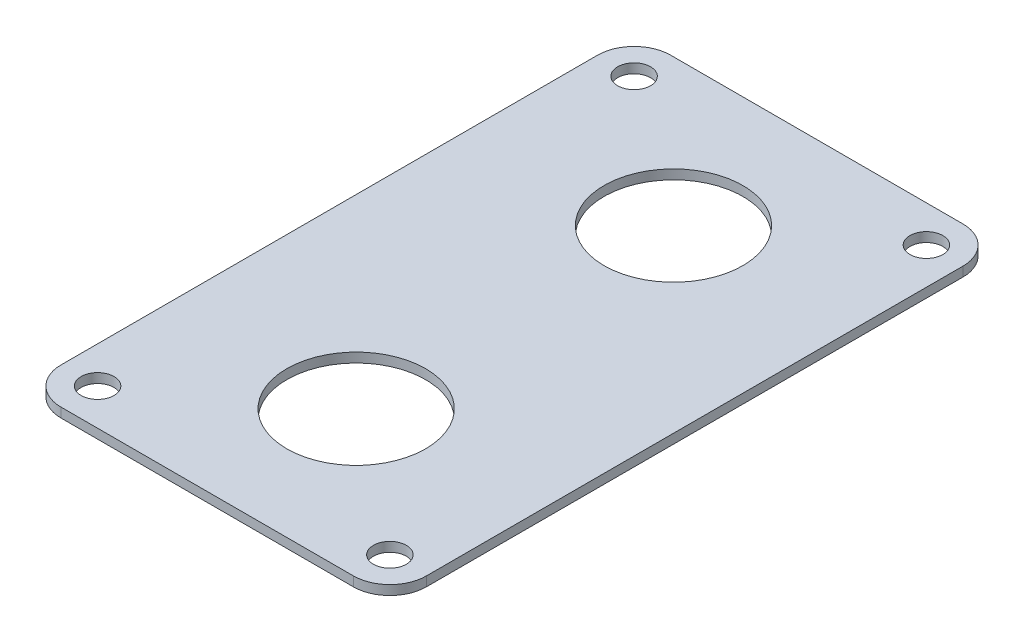
SolidWorks part; units mm, degrees
note: The reader was unsure of these and kept them because the rebuilt part matched: thickness of "Base-Flange1", "Sheet-Metal1", "Sheet-Metal2", "Sheet-Metal3".
material "AISI 1015 Steel, Cold Drawn (SS)"
ref_plane "Front Plane" through (0, 0, 0) normal (0, 0, 1) x (1, 0, 0)
ref_plane "Top Plane" through (0, 0, 0) normal (0, 1, 0) x (1, 0, 0)
ref_plane "Right Plane" through (0, 0, 0) normal (1, 0, 0) x (0, 0, -1)
sketch "Sketch1" plane through (0, 0, 0) normal (0, 1, 0) x (1, 0, 0)
  line L0 (9.6129, 37) -> (-10.3871, 37) construction
  line L1 (-25.3871, 42) -> (24.6129, 42)
  line L2 (-25.3871, 42) -> (-25.3871, -41.4143)
  line L3 (-25.3871, -41.4143) -> (24.6129, -41.4143)
  line L4 (24.6129, 42) -> (24.6129, -41.4143)
  line L6 (-20.3871, 27) -> (-20.3871, -26.4143) construction
  line L7 (19.6129, -26.4143) -> (19.6129, 27) construction
  line L9 (-10.3871, -36.4143) -> (9.6129, -36.4143) construction
  point P0 (0, 0)
  dimension "D1" = 5
  dimension "D2" = 5
  dimension "D3" = 5
  dimension "D4" = 5
base flange "Base-Flange1" sketch "Sketch1" thickness 1.3 reverse thickness direction no parameters "D1"=1.016
fillet "Fillet1" radius 5 4 edges at (24.6129, -0.65, -42) (-25.3871, -0.65, -42) (-25.3871, -0.65, 41.4143) (24.6129, -0.65, 41.4143)
sketch "Sketch6" plane through (0, 0, 0) normal (0, 1, 0) x (1, 0, 0)
  line L0 (-25.3871, 0.2928) -> (24.6129, 0.2928) construction
  line L1 (-25.3871, 37) -> (-25.3871, -36.4143) construction
  line L2 (24.6129, -36.4143) -> (24.6129, 37) construction
  circle A0 centre (0, 22) radius 9.5
  circle A1 centre (0, -21.4143) radius 9.5
  dimension "D1" = 19
  dimension "D2" = 22
extrude "Cut-Extrude1" cut sketch "Sketch6" against normal blind 10 normal cut yes
sketch "Sketch7" plane through (0, 0, 0) normal (0, 1, 0) x (1, 0, 0)
  circle A0 centre (19.6129, 37) radius 2.25
  circle A1 centre (-20.3871, 37) radius 2.25
  circle A2 centre (-20.3871, -36.4143) radius 2.25
  circle A3 centre (19.6129, -36.4143) radius 2.25
  dimension "D1" = 4.5
extrude "Cut-Extrude2" cut sketch "Sketch7" against normal blind 10 normal cut yes
sketch "Bend-Lines1" [suppressed] plane through (0, 0, 0) normal (0, 1, 0) x (1, 0, 0)
sketch "Bounding-Box1" [suppressed] plane through (0, 0, 0) normal (0, 1, 0) x (1, 0, 0)
sheet metal parameters "Sheet-Metal1" thickness 1.3 parameters "D1"=1.016, "D7"=1.52
flat pattern "Flat-Pattern1" [suppressed]
sketch "Bend-Lines2" plane through (0, 0, 0) normal (0, 1, 0) x (1, 0, 0)
sketch3d "Bounding-Box2" [suppressed]
  line L0 (-40, -20, 0) -> (40, -20, 0) construction
  line L1 (-40, 20, 0) -> (40, 20, 0) construction
  line L2 (-40, -20, 0) -> (-40, 20, 0) construction
  line L3 (40, -20, 0) -> (40, 20, 0) construction
sheet metal parameters "Sheet-Metal2" thickness 1.3 parameters "D1"=1.016, "D7"=1.52
flat pattern "Flat-Pattern1"
sketch "Bend-Lines2" plane through (0, 0, 0) normal (0, 1, 0) x (1, 0, 0)
sketch3d "Bounding-Box2" [suppressed]
  line L0 (-40, -20, 0) -> (40, -20, 0) construction
  line L1 (-40, 20, 0) -> (40, 20, 0) construction
  line L2 (-40, -20, 0) -> (-40, 20, 0) construction
  line L3 (40, -20, 0) -> (40, 20, 0) construction
sheet metal parameters "Sheet-Metal3" thickness 1.3 parameters "D1"=1.016, "D7"=1.52
flat pattern "Flat-Pattern1"
sketch "Bend-Lines2" plane through (0, 0, 0) normal (0, 1, 0) x (1, 0, 0)
sketch3d "Bounding-Box2" [suppressed]
  line L0 (-40, -20, 0) -> (40, -20, 0) construction
  line L1 (-40, 20, 0) -> (40, 20, 0) construction
  line L2 (-40, -20, 0) -> (-40, 20, 0) construction
  line L3 (40, -20, 0) -> (40, 20, 0) construction
